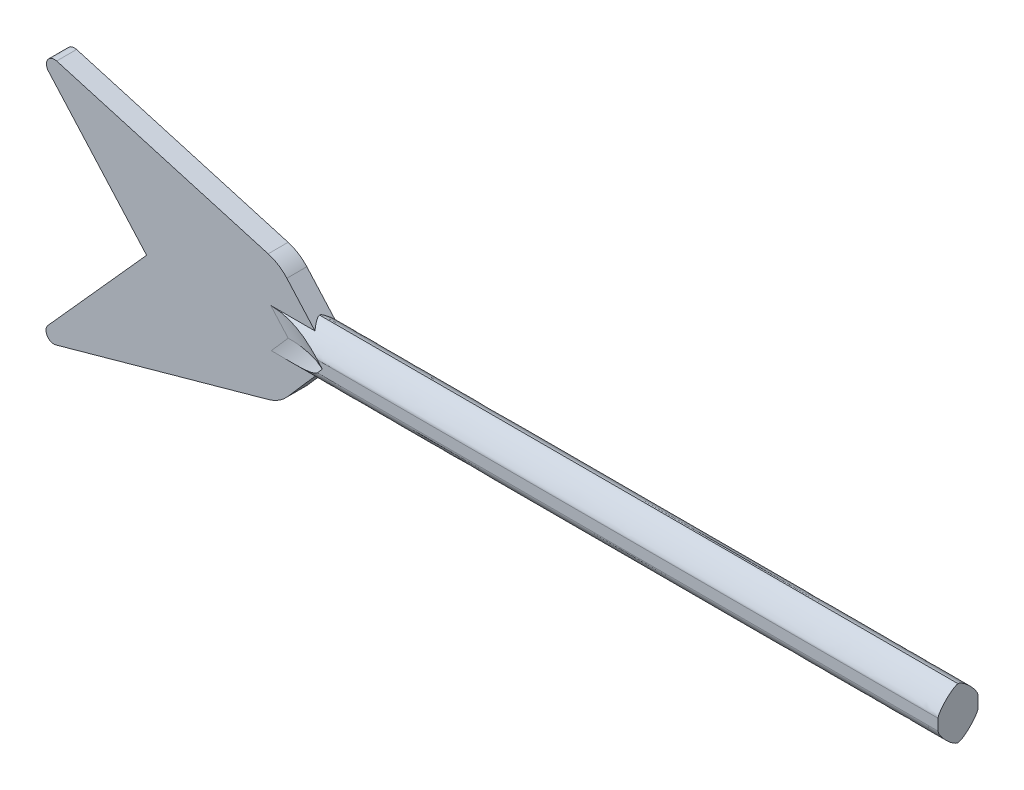
SolidWorks part; units mm, degrees
ref_plane "Plan de face" through (0, 0, 0) normal (0, 0, 1) x (1, 0, 0)
ref_plane "Plan de dessus" through (0, 0, 0) normal (0, 1, 0) x (1, 0, 0)
ref_plane "Plan de droite" through (0, 0, 0) normal (1, 0, 0) x (0, 0, -1)
sketch "Esquisse1" plane through (0, 0, 0) normal (0, 0, 1) x (1, 0, 0)
  line L0 (-12.4551, 7.3291) -> (-23.8324, 20.1144)
  line L1 (-28.5223, 23.0723) -> (-81.5296, 38.4159)
  line L2 (-83.5798, 35.1652) -> (-58.9831, 7.5246)
  line L3 (-58.9831, 7.5246) -> (-83.6838, -20.0231)
  line L4 (-81.6598, -23.2854) -> (-28.5015, -8.5304)
  line L5 (-23.6466, -5.4756) -> (-12.4551, 7.3291)
  line L9 (-18.0508, 0.9268) -> (-12.4551, 7.3291)
  arc A0 (-83.6838, -20.0231) -> (-81.6598, -23.2854) centre (-82.1948, -21.3582) ccw
  arc A1 (-81.5296, 38.4159) -> (-83.5798, 35.1652) centre (-82.0857, 36.4947) ccw
  arc A2 (-28.5015, -8.5304) -> (-23.6466, -5.4756) centre (-31.176, 1.1053) ccw
  arc A3 (-23.8324, 20.1144) -> (-28.5223, 23.0723) centre (-31.3028, 13.4666) ccw
  point P8 (-88.2489, -25.1143)
  point P11 (-88.1875, 40.343)
  point P14 (-25.6168, -7.7297)
  point P17 (-25.7506, 22.27)
  dimension "D6" = 2
  dimension "D7" = 10
  dimension "D1" = 30
  dimension "D2" = 20
  dimension "D3" = 20
  dimension "D4" = 65
  dimension "D5" = 65
  dimension "D10" = 37
  dimension "D11" = 37
extrude "Boss.-Extru.1" add sketch "Esquisse1" along normal blind 5
sketch "Esquisse2" plane through (0, 0, 0) normal (0, 0, 1) x (1, 0, 0)
  line L0 (-18.1437, 13.7217) -> (141.8563, 13.7217)
  line L1 (-12.4551, 7.3291) -> (-23.8324, 20.1144) construction
  line L2 (141.8563, 13.7217) -> (141.8563, 0.9268)
  line L3 (141.8563, 0.9268) -> (-18.0508, 0.9268)
  line L4 (-23.6466, -5.4756) -> (-12.4551, 7.3291) construction
  line L5 (-18.0508, 0.9268) -> (-12.4551, 7.3291)
  line L6 (-12.4551, 7.3291) -> (-18.1437, 13.7217)
  dimension "D1" = 160
  dimension "D2" = 12.795
extrude "Boss.-Extru.3" add sketch "Esquisse2" against normal blind 10 from offset 7.5 contours L0 L2 L3 L5 L6
fillet "Congé8" radius 15 4 edges at (-15.253, 4.1279, 5) (-15.2994, 10.5254, 5) (-15.2994, 10.5254, 0) (-15.253, 4.1279, 0)
fillet "Congé9" radius 5 4 edges at (61.9027, 0.9268, 7.5) (61.8563, 13.7217, 7.5) (61.8563, 13.7217, -2.5) (61.9027, 0.9268, -2.5)
